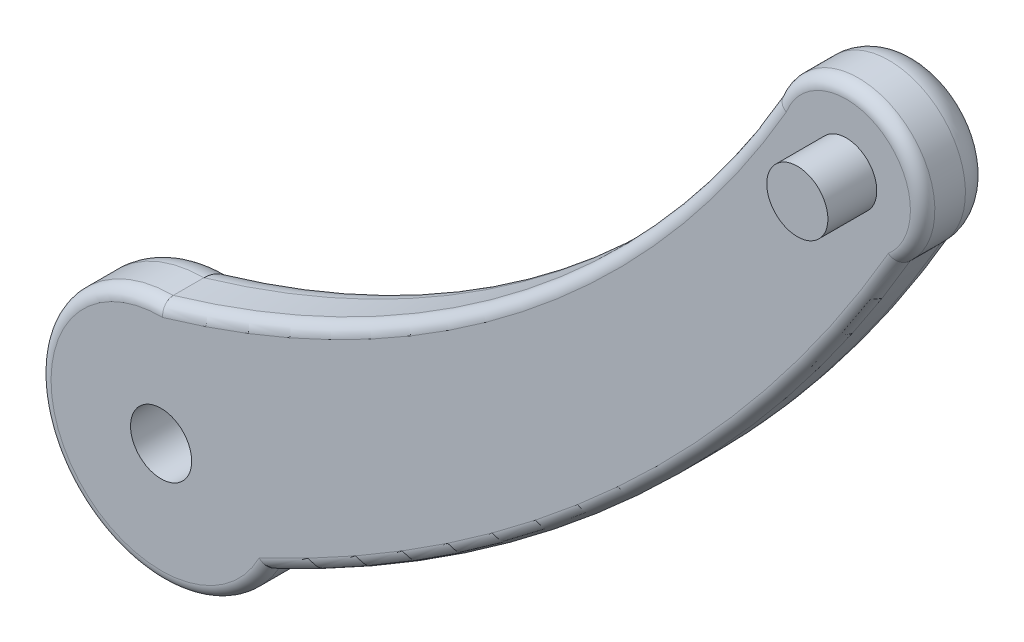
SolidWorks part; units mm, degrees
ref_plane "Front Plane" through (0, 0, 0) normal (0, 0, 1) x (1, 0, 0)
ref_plane "Top Plane" through (0, 0, 0) normal (0, 1, 0) x (1, 0, 0)
ref_plane "Right Plane" through (0, 0, 0) normal (1, 0, 0) x (0, 0, -1)
sketch "Sketch2" plane through (0, 0, 0) normal (0, 0, 1) x (1, 0, 0)
  arc A0 (0, 20) -> (17.4873, -9.7054) centre (0, 0) ccw
  arc A1 (120.5566, 85.1553) -> (100.4853, 98.9943) centre (112.0916, 94.3528) ccw
  arc A2 (100.4853, 98.9943) -> (0, 20) centre (-48.2816, 184.8256) cw
  arc A3 (17.4873, -9.7054) -> (120.5566, 85.1553) centre (-83.7656, 203.7337) ccw
  dimension "D1" = 40
  dimension "D2" = 25
extrude "Boss-Extrude1" add sketch "Sketch2" along normal blind 12
fillet "Fillet2" radius 5 4 edges at (76.2146, 29.9099, 0) (-17.2353, -10.1462, 0) (57.8648, 49.8014, 0) (119.1871, 104.6438, 0)
sketch "Sketch3" plane through (0, 0, 0) normal (0, 0, -1) x (-1, 0, 0)
  circle A0 centre (0, 0) radius 12.2527
extrude "Boss-Extrude2" add sketch "Sketch3" along normal blind 5
fillet "Fillet3" radius 5 1 edges at (-12.2527, 0, -5)
sketch "Sketch4" plane through (0, 0, -5) normal (0, 0, -1) x (-1, 0, 0)
  line L0 (0, 0) -> (0, 8.1909)
  line L3 (1, 9.1909) -> (1.7854, 12.1219)
  line L4 (-1, 9.1909) -> (-1.8289, 12.1154)
  line L5 (0, 9.1909) -> (0, 12.2527)
  circle A0 centre (0, 0) radius 12.2527 construction
  arc A1 (1.7854, 12.1219) -> (-1.8289, 12.1154) centre (0, 0) ccw
  arc A2 (-1, 9.1909) -> (1, 9.1909) centre (0, 9.1909) ccw
extrude "Cut-Extrude1" cut sketch "Sketch4" against normal blind 5 contours L4 A2 L3 A1 region at (0.0101, 10.524, -5)
pattern_circular "CirPattern1" count 7 over 360 of "Cut-Extrude1" reverse direction yes
sketch "Sketch5" plane through (0, 0, 0) normal (0, 0, -1) x (-1, 0, 0)
  circle A0 centre (0, 11.12) radius 0.7803
extrude "Boss-Extrude3" add sketch "Sketch5" along normal blind 2 contours A0
pattern_circular "CirPattern2" count 7 over 360 of "Boss-Extrude3"
sketch "Sketch6" plane through (0, 0, 0) normal (0, 0, -1) x (-1, 0, 0)
  circle A0 centre (-112.0916, 94.3528) radius 4.7456
extrude "Cut-Extrude2" cut sketch "Sketch6" against normal blind 1
fillet "Fillet4" radius 2 4 edges at (119.1871, 104.6438, 12) (76.2146, 29.9099, 12) (-17.2353, -10.1462, 12) (57.8648, 49.8014, 12)
sketch "Sketch7" plane through (0, 0, 12) normal (0, 0, 1) x (1, 0, 0)
  circle A0 centre (0, 0) radius 5
  dimension "D1" = 10
extrude "Cut-Extrude3" cut sketch "Sketch7" against normal blind 10
sketch "Sketch8" plane through (0, 0, 12) normal (0, 0, 1) x (1, 0, 0)
  circle A0 centre (112.0916, 94.3528) radius 5
  dimension "D1" = 10
extrude "Boss-Extrude4" add sketch "Sketch8" along normal blind 8
ref_plane "Plane1" through (0, -25, 0) normal (0, 1, 0) x (1, 0, 0)
sketch "Sketch10" plane through (0, -25, 0) normal (0, 1, 0) x (1, 0, 0)
  line L0 (-27.1864, -20.9496) -> (-11.683, -20.9496)
  line L1 (-11.683, -20.9496) -> (-11.683, -17.2822)
